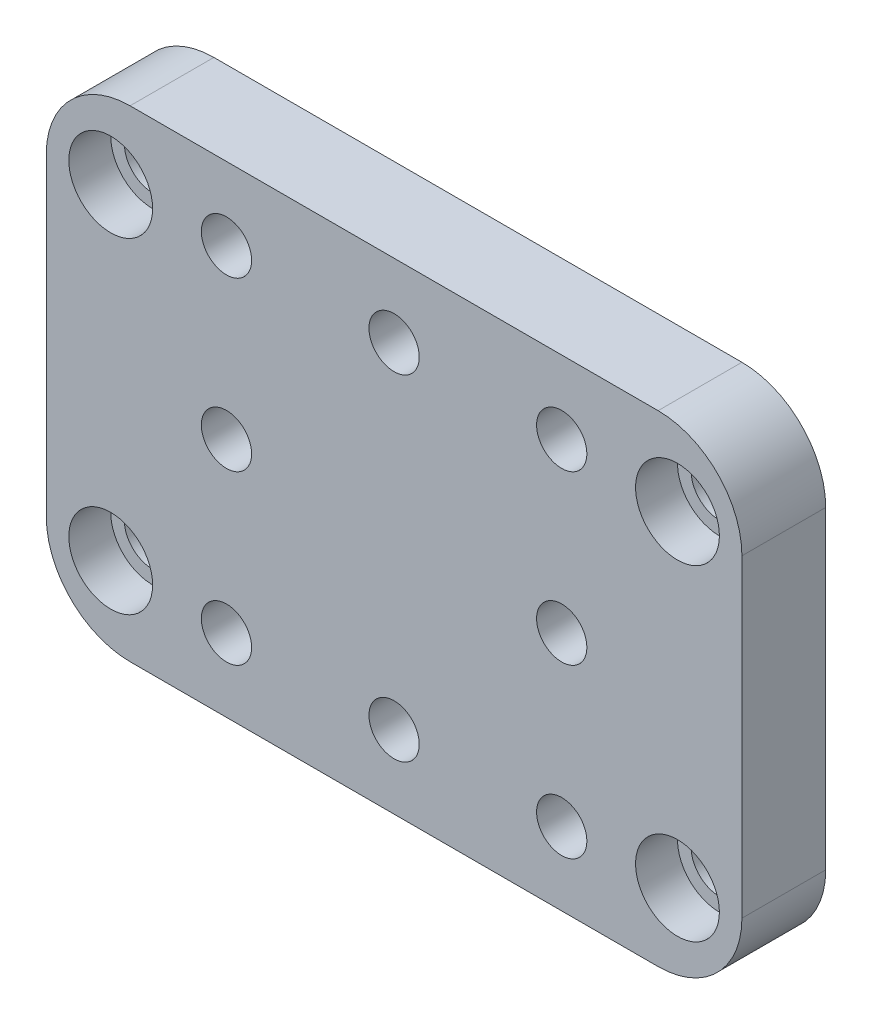
SolidWorks part; units mm, degrees
ref_plane "Alzado" through (0, 0, 0) normal (0, 0, 1) x (1, 0, 0)
ref_plane "Planta" through (0, 0, 0) normal (0, 1, 0) x (1, 0, 0)
ref_plane "Vista lateral" through (0, 0, 0) normal (1, 0, 0) x (0, 0, -1)
sketch "Croquis1" plane through (0, 0, 0) normal (0, 0, 1) x (1, 0, 0)
  line L0 (-0.0106, 23.1539) -> (33.1904, 23.1539)
  line L5 (-0.0106, 23.1539) -> (-0.0106, 0.1756)
  line L6 (-0.0106, 0.1756) -> (33.1904, 0.1756)
  line L7 (33.1904, 23.1539) -> (33.1904, 0.1756)
  circle A0 centre (3.0649, 19.4414) radius 1.3479
  circle A1 centre (30.1148, 19.4414) radius 1.35
  circle A2 centre (30.1148, 3.8881) radius 1.35
  circle A3 centre (3.0649, 3.8881) radius 1.3526
extrude "Saliente-Extruir1" add sketch "Croquis1" along normal blind 4 contours L0 L7 L6 L5
sketch "Croquis3" plane through (0, 0, 0) normal (0, 0, -1) x (-1, 0, 0)
  circle A0 centre (-30.1148, 19.4414) radius 1.35
  circle A1 centre (-3.0649, 19.4414) radius 1.3479
  circle A2 centre (-3.0649, 3.8881) radius 1.3526
  circle A3 centre (-30.1148, 3.8881) radius 1.35
extrude "Cortar-Extruir2" cut sketch "Croquis3" against normal through all
fillet "Redondeo2" radius 4 2 edges at (33.1904, 0.1756, 2) (33.1904, 23.1539, 2)
fillet "Redondeo3" radius 4 2 edges at (-0.0106, 0.1756, 2) (-0.0106, 23.1539, 2)
sketch "Croquis4" plane through (0, 0, 4) normal (0, 0, 1) x (1, 0, 0)
  line L0 (16.5899, 3.6647) -> (16.5899, 0.1756) construction
  line L1 (8.5899, 19.6647) -> (24.5899, 19.6647)
  line L2 (8.5899, 19.6647) -> (8.5899, 3.6647)
  line L3 (8.5899, 3.6647) -> (24.5899, 3.6647)
  line L4 (24.5899, 19.6647) -> (24.5899, 3.6647)
  line L5 (3.9894, 0.1756) -> (29.1904, 0.1756) construction
  line L6 (16.5899, 23.1539) -> (16.5899, 19.6647) construction
  line L7 (24.5899, 11.6647) -> (33.1904, 11.6647) construction
  line L8 (33.1904, 19.1539) -> (33.1904, 4.1756) construction
  line L9 (3.9894, 23.1539) -> (29.1904, 23.1539) construction
  line L10 (8.5899, 11.6647) -> (-0.0106, 11.6647) construction
  line L11 (-0.0106, 19.1539) -> (-0.0106, 4.1756) construction
  circle A0 centre (8.5899, 19.6647) radius 1.2
  circle A1 centre (16.5899, 19.6647) radius 1.2
  circle A2 centre (24.5899, 19.6647) radius 1.2
  circle A3 centre (8.5899, 11.6647) radius 1.2
  circle A4 centre (24.5899, 11.6647) radius 1.2
  circle A5 centre (8.5899, 3.6647) radius 1.2
  circle A6 centre (16.5899, 3.6647) radius 1.2
  circle A7 centre (24.5899, 3.6647) radius 1.2
  dimension "D1" = 16
extrude "Cortar-Extruir3" cut sketch "Croquis4" against normal through all contours L1 A0 L2 | L2 A0 L1 | L2 A3 | L2 A3 | L2 A5 L3 | L3 A5 L2 | L3 A6 | L3 A6 | L3 A7 L4 | L4 A7 L3 | L4 A4 | L4 A4 | L4 A2 L1 | L1 A2 L4 | L1 A1 | L1 A1 region at (8.4201, 19.8345, 4) region at (9.0992, 19.1554, 4) region at (16.5899, 20.174, 4) region at (16.5899, 19.1554, 4) region at (9.0992, 11.6647, 4) region at (8.0806, 11.6647, 4) region at (24.7596, 19.8345, 4) region at (24.0806, 19.1554, 4) region at (9.0992, 4.174, 4) region at (8.4201, 3.495, 4) region at (25.0992, 11.6647, 4) region at (24.0806, 11.6647, 4) region at (16.5899, 4.174, 4) region at (16.5899, 3.1554, 4) region at (24.7596, 3.495, 4) region at (24.0806, 4.174, 4)
sketch "Croquis5" plane through (0, 0, 4) normal (0, 0, 1) x (1, 0, 0)
  circle A0 centre (3.0649, 19.4414) radius 2
  circle A1 centre (30.1148, 19.4414) radius 2
  circle A2 centre (30.1148, 3.8881) radius 2
  circle A3 centre (3.0649, 3.8881) radius 2
extrude "Cortar-Extruir4" cut sketch "Croquis5" against normal blind 2
